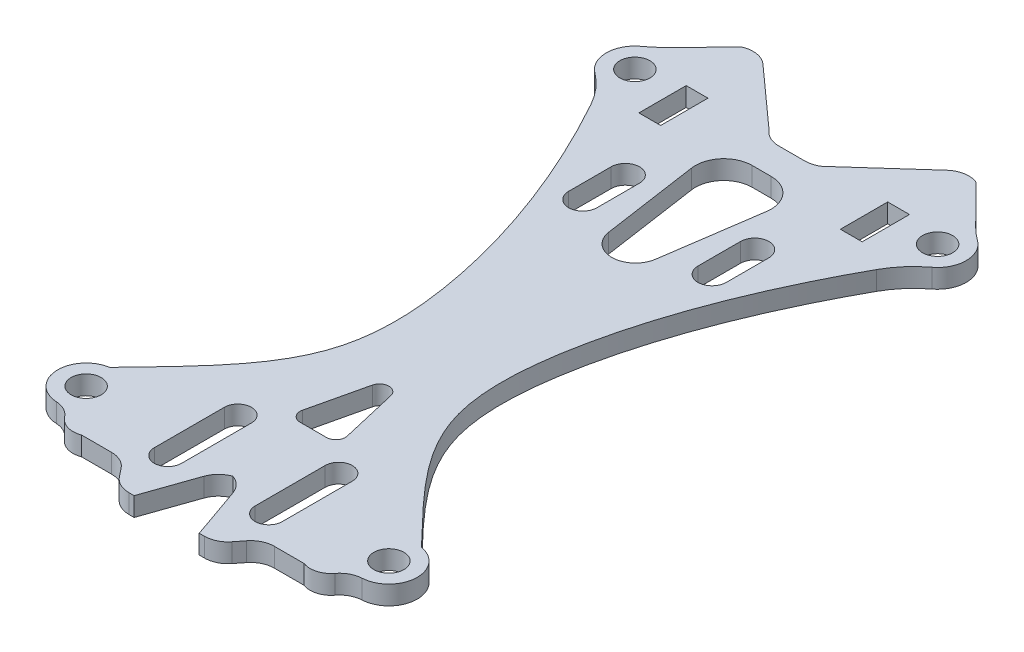
SolidWorks part; units mm, degrees
ref_plane "Alzado" through (0, 0, 0) normal (0, 0, 1) x (1, 0, 0)
ref_plane "Planta" through (0, 0, 0) normal (0, 1, 0) x (1, 0, 0)
ref_plane "Vista lateral" through (0, 0, 0) normal (1, 0, 0) x (0, 0, -1)
sketch "Croquis1" plane through (0, 0, 0) normal (0, 1, 0) x (1, 0, 0)
  line L0 (0, 0) -> (0, -2.5005) construction
  line L1 (-16.4807, 34.3089) -> (-12.3604, 38.4652)
  line L2 (-3.6329, -113.0793) -> (172.3671, -113.0793) construction
  line L3 (16.4807, 34.3089) -> (12.3604, 38.4652)
  line L6 (-1.3883, 31.3579) -> (-0.0407, 31.3579)
  line L14 (-6.6341, -32.9023) -> (-5.9532, -33.7675)
  line L15 (-3.9886, -34.7215) -> (-3.4412, -34.7215)
  line L16 (-3.4412, -34.7215) -> (-1.5339, -29.2621)
  line L17 (-5.3289, -21.8677) -> (-5.3289, -29.2621) construction
  line L18 (-3.8938, -21.8677) -> (-3.8938, -29.2621)
  line L19 (3.4412, -34.7215) -> (1.5339, -29.2621)
  line L20 (3.9886, -34.7215) -> (3.4412, -34.7215)
  line L21 (6.6341, -32.9023) -> (5.9532, -33.7675)
  line L22 (11.7582, -31.9483) -> (8.5987, -31.9483)
  line L27 (-1.3938, -19.2314) -> (1.3938, -19.2314)
  line L28 (1.3883, 31.3579) -> (0.0407, 31.3579)
  line L29 (3.3225, 32.274) -> (9.7209, 38.0206)
  line L30 (-3.3225, 32.274) -> (-9.7209, 38.0206)
  line L32 (-0.0407, 31.3579) -> (0.0407, 31.3579)
  line L33 (-6.7639, -21.8677) -> (-6.7639, -29.2621)
  line L34 (-6.8365, 20.5928) -> (-6.8365, 16.0956) construction
  line L35 (-5.3372, 20.5928) -> (-5.3372, 16.0956)
  line L36 (-8.3358, 20.5928) -> (-8.3358, 16.0956)
  line L37 (5.3289, -21.8677) -> (5.3289, -29.2621) construction
  line L38 (3.8938, -21.8677) -> (3.8938, -29.2621)
  line L39 (6.7639, -21.8677) -> (6.7639, -29.2621)
  line L40 (6.8365, 20.5928) -> (6.8365, 16.0956) construction
  line L41 (5.3372, 20.5928) -> (5.3372, 16.0956)
  line L42 (8.3358, 20.5928) -> (8.3358, 16.0956)
  line L43 (-0.9741, -12.0051) -> (-2.3679, -18.0051)
  line L46 (0.9741, -12.0051) -> (2.3679, -18.0051)
  line L47 (-1.0018, 28.1672) -> (1.0018, 28.1672)
  line L48 (3.9704, 24.7344) -> (2.4738, 14.4687)
  line L49 (-3.9704, 24.7344) -> (-2.4738, 14.4687)
  line L58 (-11.7582, -31.9483) -> (-8.5987, -31.9483)
  line L59 (-11.8, 31.9896) -> (-9.5, 31.9896)
  line L60 (-11.8, 31.9896) -> (-11.8, 26.9896)
  line L61 (-11.8, 26.9896) -> (-9.5, 26.9896)
  line L62 (-9.5, 31.9896) -> (-9.5, 26.9896)
  line L63 (11.8, 31.9896) -> (9.5, 31.9896)
  line L64 (11.8, 31.9896) -> (11.8, 26.9896)
  line L65 (9.5, 31.9896) -> (9.5, 26.9896)
  line L66 (11.8, 26.9896) -> (9.5, 26.9896)
  arc A9 (-3.3225, 32.274) -> (-1.3883, 31.3579) centre (-1.3883, 33.8579) ccw
  arc A10 (0, -27.7272) -> (-1.5339, -29.2621) centre (0.8263, -30.0867) ccw
  arc A11 (-3.9886, -34.7215) -> (-5.9532, -33.7675) centre (-3.9886, -32.2215) cw
  arc A14 (11.7582, -31.9483) -> (14.2972, -31.2145) centre (12.5343, -29.8741) ccw
  arc A15 (6.6341, -32.9023) -> (8.5987, -31.9483) centre (8.5987, -34.4483) cw
  arc A16 (3.9886, -34.7215) -> (5.9532, -33.7675) centre (3.9886, -32.2215) ccw
  arc A17 (0, -27.7272) -> (1.5339, -29.2621) centre (-0.8263, -30.0867) cw
  arc A18 (3.3225, 32.274) -> (1.3883, 31.3579) centre (1.3883, 33.8579) cw
  arc A24 (-3.8938, -21.8677) -> (-6.7639, -21.8677) centre (-5.3289, -21.8677) ccw
  arc A25 (-6.7639, -29.2621) -> (-3.8938, -29.2621) centre (-5.3289, -29.2621) ccw
  arc A26 (-5.3372, 20.5928) -> (-8.3358, 20.5928) centre (-6.8365, 20.5928) ccw
  arc A27 (-8.3358, 16.0956) -> (-5.3372, 16.0956) centre (-6.8365, 16.0956) ccw
  arc A28 (3.8938, -21.8677) -> (6.7639, -21.8677) centre (5.3289, -21.8677) cw
  arc A29 (6.7639, -29.2621) -> (3.8938, -29.2621) centre (5.3289, -29.2621) cw
  arc A30 (5.3372, 20.5928) -> (8.3358, 20.5928) centre (6.8365, 20.5928) cw
  arc A31 (8.3358, 16.0956) -> (5.3372, 16.0956) centre (6.8365, 16.0956) cw
  arc A32 (0.9741, -12.0051) -> (-0.9741, -12.0051) centre (0, -12.2314) ccw
  arc A33 (1.3938, -19.2314) -> (2.3679, -18.0051) centre (1.3938, -18.2314) ccw
  arc A34 (-2.3679, -18.0051) -> (-1.3938, -19.2314) centre (-1.3938, -18.2314) ccw
  arc A35 (1.0018, 28.1672) -> (3.9704, 24.7344) centre (1.0018, 25.1672) cw
  arc A36 (-1.0018, 28.1672) -> (-3.9704, 24.7344) centre (-1.0018, 25.1672) ccw
  arc A37 (2.4738, 14.4687) -> (-2.4738, 14.4687) centre (0, 14.8294) cw
  arc A38 (-9.7209, 38.0206) -> (-12.3604, 38.4652) centre (-11.3914, 36.1606) ccw
  arc A40 (9.7209, 38.0206) -> (12.3604, 38.4652) centre (11.3914, 36.1606) cw
  circle A43 centre (16, -27.2352) radius 1.5875
  arc A49 (14.2972, -31.2145) -> (16.1567, -30.2311) centre (16.2872, -32.7277) cw
  circle A50 centre (16, 30.7648) radius 3.02 construction
  arc A54 (16.48, -24.2739) -> (16.1567, -30.2311) centre (16, -27.2352) cw
  circle A55 centre (-16, 30.7648) radius 1.5875
  circle A56 centre (16, 30.7648) radius 1.5875
  arc A57 (17.8212, 28.3557) -> (17.7588, 33.2198) centre (16, 30.7648) ccw
  arc A58 (-17.8212, 28.3557) -> (-17.7588, 33.2198) centre (-16, 30.7648) cw
  arc A59 (17.7588, 33.2198) -> (16.4807, 34.3089) centre (23.5825, 41.349) cw
  arc A60 (-17.7588, 33.2198) -> (-16.4807, 34.3089) centre (-23.5825, 41.349) ccw
  arc A61 (-15.1003, 25.2176) -> (-17.8212, 28.3557) centre (-23.8515, 20.3786) ccw
  arc A62 (15.1003, 25.2176) -> (17.8212, 28.3557) centre (23.8515, 20.3786) cw
  circle A63 centre (-16, -27.2352) radius 1.5875
  arc A64 (-6.6341, -32.9023) -> (-8.5987, -31.9483) centre (-8.5987, -34.4483) ccw
  arc A65 (-11.7582, -31.9483) -> (-14.2972, -31.2145) centre (-12.5343, -29.8741) cw
  arc A66 (-16.48, -24.2739) -> (-16.1567, -30.2311) centre (-16, -27.2352) ccw
  arc A67 (-14.2972, -31.2145) -> (-16.1567, -30.2311) centre (-16.2872, -32.7277) ccw
  spline S1 degree 3 poles (16.48, -24.2739) (11.4037, -18.9858) (4.6463, -12.29) (6.3337, 7.0236) (11.6361, 18.9525) (15.1003, 25.2176) knots 0 0 0 0 0.308743 0.525126 0.939196 0.939196 0.939196 0.939196
  spline S2 degree 3 poles (-16.48, -24.2739) (-11.4037, -18.9858) (-4.6463, -12.29) (-6.3337, 7.0236) (-11.6361, 18.9525) (-15.1003, 25.2176) knots 0 0 0 0 0.308743 0.525126 0.939196 0.939196 0.939196 0.939196
  point P15 (-5.3289, -25.5649)
  point P27 (-12.05, 29.4649)
  point P31 (14.7472, -29.9611)
  point P52 (-6.8365, 18.3442)
  point P88 (17.2845, 33.498)
  point P92 (5.3289, -25.5649)
  point P99 (6.8365, 18.3442)
  point P111 (0, -7.812)
  point P114 (2.6528, -19.2314)
  point P117 (-2.6528, -19.2314)
  point P121 (-17.2845, 33.498)
  point P123 (4.4709, 28.1672)
  point P126 (-4.4709, 28.1672)
  point P146 (-14.7472, -29.9611)
  dimension "D4" = 2.5
  dimension "D5" = 2.5
  dimension "D6" = 2.5
  dimension "D7" = 2.5
  dimension "D8" = 1
  dimension "D10" = 3
  dimension "D11" = 2.5
  dimension "D2" = 10
  dimension "D3" = 3.175
  dimension "D14" = 2.5
  dimension "D12" = 16
  dimension "D18" = 10
  dimension "D19" = 10
  dimension "D9" = 6
  dimension "D13" = 2.3
  dimension "D15" = 5
  dimension "D17" = 9.5
extrude "Saliente-Extruir2" add sketch "Croquis1" along normal blind 2
